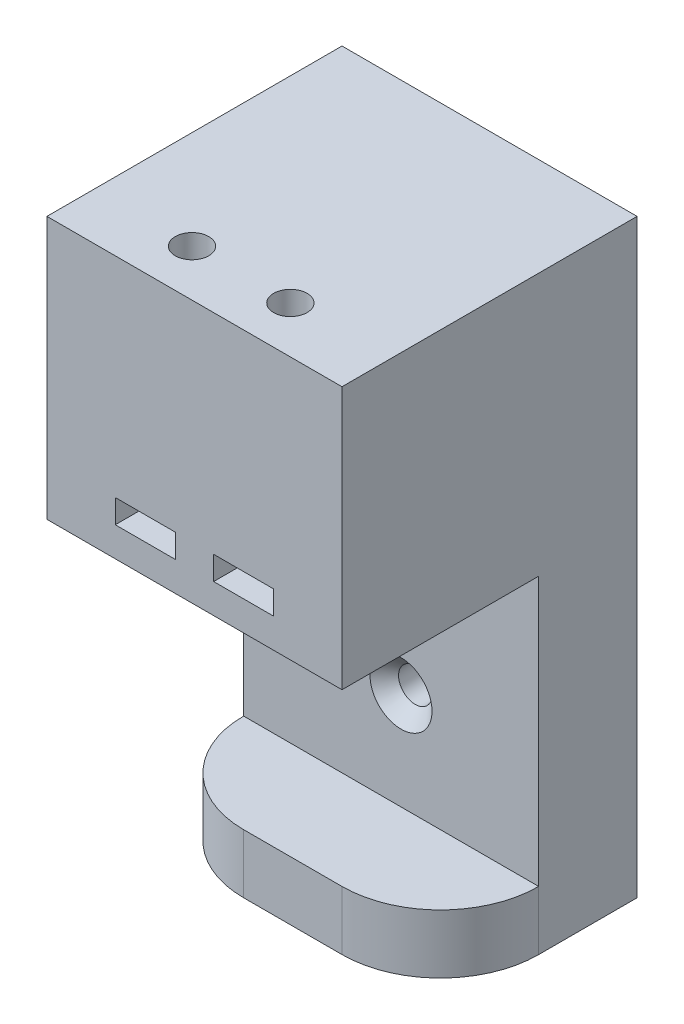
SolidWorks part; units mm, degrees
ref_plane "Plan de face" through (0, 0, 0) normal (0, 0, 1) x (1, 0, 0)
ref_plane "Plan de dessus" through (0, 0, 0) normal (0, 1, 0) x (1, 0, 0)
ref_plane "Plan de droite" through (0, 0, 0) normal (1, 0, 0) x (0, 0, -1)
sketch "Esquisse1" plane through (0, 0, 0) normal (0, 0, 1) x (1, 0, 0)
  line L1 (0, 0) -> (30, 0)
  line L2 (0, 0) -> (0, 60)
  line L3 (0, 60) -> (30, 60)
  line L4 (30, 0) -> (30, 60)
  dimension "D1" = 30
  dimension "D2" = 60
extrude "Boss.-Extru.1" add sketch "Esquisse1" along normal blind 10
sketch "Esquisse2" plane through (0, 0, 10) normal (0, 0, 1) x (1, 0, 0)
  line L0 (30, 0) -> (30, 60) construction
  line L1 (0, 0) -> (30, 0) construction
  line L2 (0, 60) -> (0, 0) construction
  line L3 (30, 0) -> (30, 6)
  line L4 (0, 0) -> (30, 0)
  line L5 (0, 6) -> (0, 0)
  line L6 (0, 6) -> (30, 6)
  dimension "D1" = 6
extrude "Boss.-Extru.2" add sketch "Esquisse2" along normal blind 10
sketch "Esquisse3" plane through (0, 0, 0) normal (0, -1, 0) x (1, 0, 0)
  line L0 (0, 20) -> (0, 0) construction
  line L1 (0, 0) -> (30, 0) construction
  circle A0 centre (15, 60) radius 4
  dimension "D3" = 8
  dimension "D1" = 15
  dimension "D2" = 60
extrude "Enlèv. mat.-Extru.1" [suppressed] cut sketch "Esquisse3" against normal up to surface (6 mm away) up to face at (15, 6, 15)
sketch "Esquisse4" plane through (0, 0, 10) normal (0, 0, 1) x (1, 0, 0)
  line L0 (30, 6) -> (30, 60) construction
  line L1 (30, 33.32) -> (30, 60)
  line L2 (0, 60) -> (0, 6) construction
  line L3 (30, 60) -> (0, 60) construction
  line L4 (0, 60) -> (0, 33.32)
  line L5 (30, 60) -> (0, 60)
  line L6 (0, 33.32) -> (30, 33.32)
  line L8 (30, 6) -> (0, 6) construction
  dimension "D1" = 27.32
extrude "Boss.-Extru.3" add sketch "Esquisse4" along normal blind 20
sketch "Esquisse5" plane through (0, 33.32, 0) normal (0, -1, 0) x (1, 0, 0)
  line L0 (0, 30) -> (0, 10) construction
  line L2 (0, 30) -> (30, 30) construction
  circle A0 centre (10, 25.25) radius 2.2
  circle A1 centre (20, 25.25) radius 2.2
  dimension "D3" = 4.4
  dimension "D4" = 4.4
  dimension "D1" = 10
  dimension "D2" = 10
  dimension "D5" = 4.75
  dimension "D6" = 4.75
hole_wizard "Dégagement M31" positions "Esquisse8" profile "Esquisse7" hole size "M3" standard "ISO"
sketch "Esquisse8" plane through (0, 33.32, 0) normal (0, -1, 0) x (-1, 0, 0)
  point P0 (-10, -25.25)
  point P3 (-20, -25.25)
sketch "Esquisse7" plane through (10, 33.32, 25.25) normal (1, 0, 0) x (0, 0, -1)
  line L0 (0, 0) -> (0, 27.7015)
  line L1 (0, 27.7015) -> (1.7, 26.68)
  line L2 (1.7, 26.68) -> (1.7, 0)
  line L5 (1.7, 0) -> (0, 0)
  line L10 (0, 27.7015) -> (-1.7, 26.68) construction
  line L11 (0, -6.35) -> (0, 107.95) construction
  dimension "Diamètre du perçage" = 3.4
  dimension "Profondeur du perçage" = 26.68
  dimension "Angle de pointe" = 118
sketch "Esquisse9" plane through (0, 0, 10) normal (0, 0, 1) x (1, 0, 0)
  line L0 (0, 33.32) -> (0, 6) construction
  line L1 (30, 6) -> (30, 33.32) construction
  line L2 (30, 6) -> (0, 6) construction
  line L3 (0, 33.32) -> (30, 33.32) construction
  circle A1 centre (16, 16) radius 1.5
  circle A2 centre (10, 23.32) radius 1.5
  dimension "D2" = 3
  dimension "D4" = 3
  dimension "D1" = 10
  dimension "D3" = 14
  dimension "D5" = 10
  dimension "D6" = 10
hole_wizard "Fraisage pour vis à tête fraisée M31" positions "Esquisse10" profile "Esquisse12" countersink size "M3" standard "ISO"
sketch "Esquisse10" plane through (0, 0, 10) normal (0, 0, 1) x (1, 0, 0)
  point P0 (10, 23.32)
  point P3 (16, 16)
sketch "Esquisse12" plane through (10, 23.32, 10) normal (1, 0, 0) x (0, -1, 0)
  line L0 (0, 0) -> (0, 11.0215)
  line L1 (0, 11.0215) -> (1.7, 10)
  line L2 (1.7, 10) -> (1.7, 1.45)
  line L3 (1.7, 1.45) -> (3.15, 0)
  line L5 (3.15, 0) -> (0, 0)
  line L6 (-1.7, 1.45) -> (-3.15, 0) construction
  line L10 (0, 11.0215) -> (-1.7, 10) construction
  line L11 (0, -6.35) -> (0, 107.95) construction
  dimension "Diamètre du perçage" = 3.4
  dimension "Profondeur du perçage" = 10
  dimension "Diamètre du fraisage entrant" = 6.3
  dimension "Angle du fraisage entrant" = 90
  dimension "Angle de pointe" = 118
fillet "Congé1" radius 10 2 edges at (30, 3, 20) (0, 3, 20)
sketch "Esquisse13" plane through (0, 0, 30) normal (0, 0, 1) x (1, 0, 0)
  line L0 (0, 33.32) -> (30, 33.32) construction
  line L1 (6.95, 38.72) -> (13.05, 38.72)
  line L2 (6.95, 38.72) -> (6.95, 36.32)
  line L3 (6.95, 36.32) -> (13.05, 36.32)
  line L4 (13.05, 38.72) -> (13.05, 36.32)
  line L5 (23.05, 38.72) -> (16.95, 38.72)
  line L6 (23.05, 38.72) -> (23.05, 36.32)
  line L7 (23.05, 36.32) -> (16.95, 36.32)
  line L8 (16.95, 38.72) -> (16.95, 36.32)
  line L9 (0, 60) -> (0, 33.32) construction
  line L10 (30, 33.32) -> (30, 60) construction
  point P10 (10, 38.72)
  point P13 (20, 38.72)
  dimension "D1" = 3
  dimension "D2" = 3
  dimension "D3" = 10
  dimension "D4" = 10
  dimension "D5" = 6.1
  dimension "D6" = 6.1
  dimension "D7" = 2.4
  dimension "D8" = 2.4
extrude "Enlèv. mat.-Extru.2" cut sketch "Esquisse13" against normal blind 8.45
equation "\"D4@Esquisse5\"=\"D3@Esquisse5\""
equation "\"D6@Esquisse5\"=\"D5@Esquisse5\""
